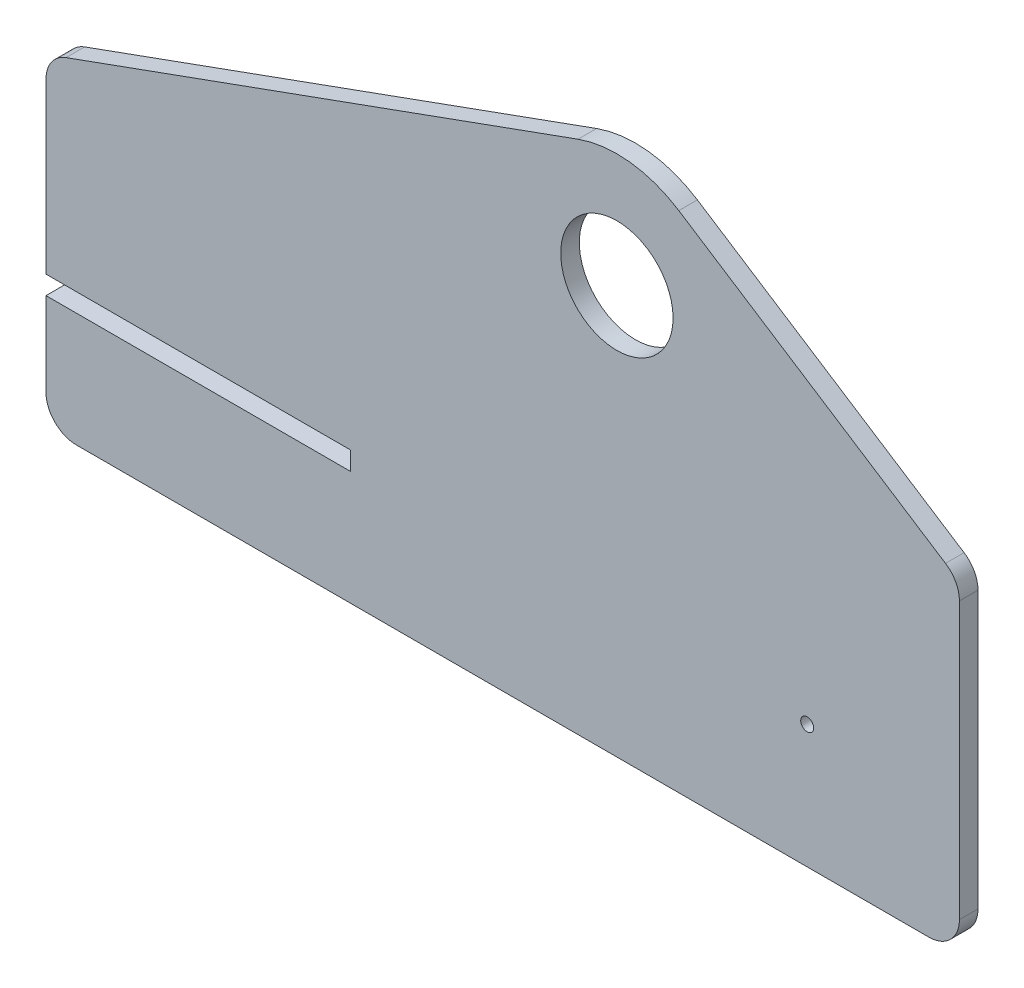
SolidWorks part; units mm, degrees
material "Corrugated Paper"
ref_plane "Front Plane" through (0, 0, 0) normal (0, 0, 1) x (1, 0, 0)
ref_plane "Top Plane" through (0, 0, 0) normal (0, 1, 0) x (1, 0, 0)
ref_plane "Right Plane" through (0, 0, 0) normal (1, 0, 0) x (0, 0, -1)
sketch "Sketch2" plane through (0, 0, 0) normal (0, 0, 1) x (1, 0, 0)
  line L0 (-50.8, 1.5494) -> (-50.8, 7.8994)
  line L1 (-50.8, -7.8994) -> (50.8, -7.8994)
  line L2 (-50.8, -7.8994) -> (-50.8, -1.5494)
  line L3 (-50.8, 7.8994) -> (50.8, 7.8994)
  line L4 (50.8, -7.8994) -> (50.8, 7.8994)
  line L5 (-50.8, -7.8994) -> (50.8, 7.8994) construction
  line L6 (-50.8, 7.8994) -> (50.8, -7.8994) construction
  line L7 (-50.8, 1.5494) -> (0, 1.5494)
  line L9 (-50.8, -1.5494) -> (0, -1.5494)
  line L10 (0, 1.5494) -> (0, -1.5494)
  point P0 (0, 0)
  dimension "D1" = 50.8
  dimension "D3" = 3.0988
  dimension "D2" = 6.35
extrude "Boss-Extrude1" add sketch "Sketch2" along normal blind 3.0988
sketch "Sketch3" plane through (0, 0, 0) normal (0, 0, 1) x (1, 0, 0)
  line L0 (-50.8, -7.8994) -> (-50.8, -20.5994)
  line L1 (-50.8, -20.5994) -> (101.6, -20.5994)
  line L2 (101.6, -20.5994) -> (101.6, 33.2994)
  line L3 (50.8, 7.8994) -> (-50.8, 7.8994) construction
  line L5 (-50.8, 33.2994) -> (-50.8, 7.8994)
  line L6 (-50.8, -7.8994) -> (50.8, -7.8994) construction
  line L7 (50.8, -7.8994) -> (50.8, 7.8994) construction
  line L8 (-50.8, -7.8994) -> (50.8, -7.8994)
  line L9 (50.8, -7.8994) -> (50.8, 7.8994)
  line L10 (50.8, 7.8994) -> (-50.8, 7.8994)
  line L12 (54.7822, 63.5237) -> (101.6, 33.2994)
  line L13 (37.9659, 65.4316) -> (-50.8, 33.2994)
  circle A0 centre (76.2, 0) radius 1.0795
  circle A1 centre (44.45, 47.519) radius 9.3726
  arc A2 (54.7822, 63.5237) -> (37.9659, 65.4316) centre (44.45, 47.519) ccw
  dimension "D1" = 2.159
  dimension "D7" = 38.1
  dimension "D8" = 18.7452
  dimension "D2" = 12.7
  dimension "D3" = 25.4
  dimension "D4" = 152.4
  dimension "D5" = 25.4
  dimension "D6" = 57.15
  dimension "D9" = 31.75
extrude "Boss-Extrude2" add sketch "Sketch3" along normal blind 3.0988 contours L10 L9 L8 L0 L1 L2 L5 A0 region at (31.4277, 17.7147, 0)
fillet "Fillet1" radius 5.08 4 edges at (101.6, 33.2994, 1.5494) (101.6, -20.5994, 1.5494) (-50.8, -20.5994, 1.5494) (-50.8, 33.2994, 1.5494)
equation "\"rodThick\"= 0.085in"
equation "\"thick\"= 0.122in"
equation "\"clear\"= 0.003in"
equation "\"D3@Sketch2\"=\"thick\""
equation "\"D1@Boss-Extrude1\"=\"thick\""
equation "\"D1@Sketch3\"=\"rodThick\""
equation "\"D1@Boss-Extrude2\"=\"thick\""
